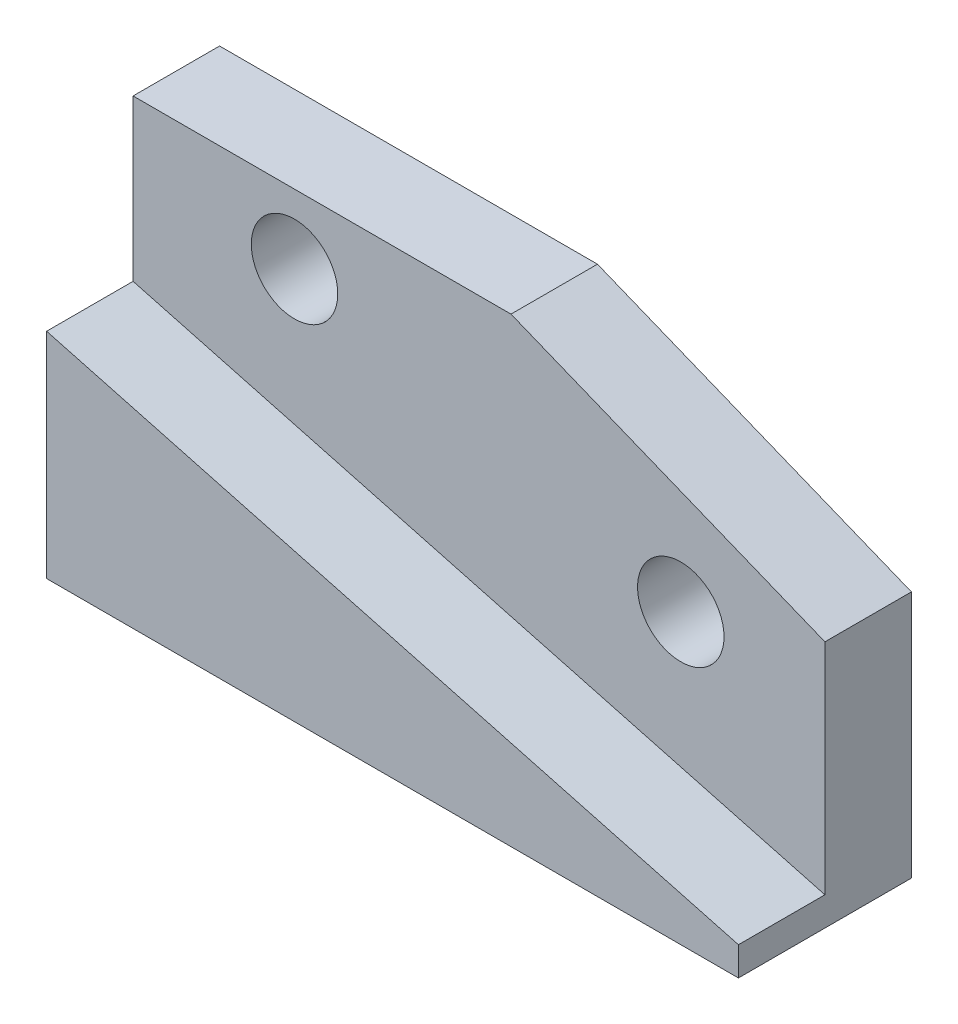
SolidWorks part; units mm, degrees
material "1060 Alloy"
ref_plane "Front Plane" through (0, 0, 0) normal (0, 0, 1) x (1, 0, 0)
ref_plane "Top Plane" through (0, 0, 0) normal (0, 1, 0) x (1, 0, 0)
ref_plane "Right Plane" through (0, 0, 0) normal (1, 0, 0) x (0, 0, -1)
sketch "Sketch1" plane through (0, 0, 0) normal (0, 0, 1) x (1, 0, 0)
  line L0 (60, -27.5) -> (-60, 4.6539)
  line L1 (5.5481, 32.5) -> (-60, 32.5)
  line L2 (60, 10.5) -> (60, -32.5)
  line L3 (60, -32.5) -> (-60, -32.5)
  line L4 (-60, 32.5) -> (-60, -32.5)
  line L5 (60, 32.5) -> (-60, -32.5) construction
  line L6 (60, -32.5) -> (-60, 32.5) construction
  line L7 (5.5481, 32.5) -> (60, 10.5)
  circle A0 centre (-32, 20.5) radius 7.5
  circle A1 centre (35, 2.5) radius 7.5
  point P1 (0, 0)
  dimension "D7" = 15
  dimension "D9" = 28
  dimension "D10" = 15
  dimension "D1" = 120
  dimension "D2" = 65
  dimension "D3" = 15
  dimension "D4" = 5
  dimension "D5" = 22
  dimension "D6" = 68
  dimension "D8" = 12
  dimension "D11" = 25
  dimension "D12" = 30
extrude "Boss-Extrude1" add sketch "Sketch1" along normal blind 15 contours L0 L4 L3 L2 region at (-15.2555, -19.9177, 0)
extrude "Boss-Extrude5" add sketch "Sketch1<7>" against normal blind 15 contours A0 | A1 | L4 L3 L2 L7 L1 region at (-32, 20.5, 0) region at (35, 2.5, 0)
sketch "Sketch1<7>" plane through (0, 0, 0) normal (0, 0, 1) x (1, 0, 0) same geometry as "Sketch1"
